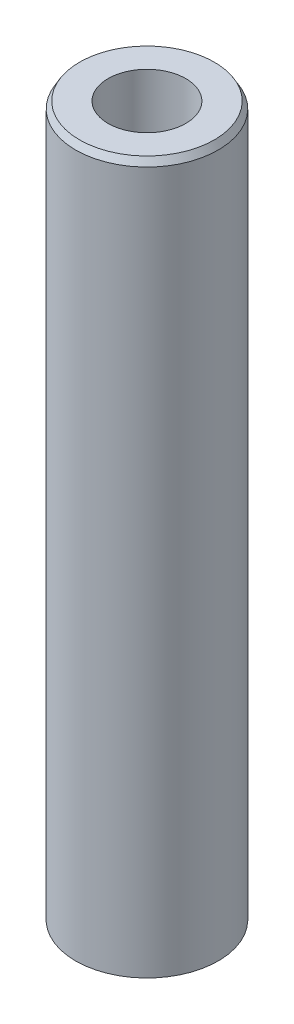
SolidWorks part; units mm, degrees
ref_plane "Front Plane" through (0, 0, 0) normal (0, 0, 1) x (1, 0, 0)
ref_plane "Top Plane" through (0, 0, 0) normal (0, 1, 0) x (1, 0, 0)
ref_plane "Right Plane" through (0, 0, 0) normal (1, 0, 0) x (0, 0, -1)
sketch "Sketch1" plane through (0, 0, 0) normal (0, 1, 0) x (1, 0, 0)
  circle A0 centre (0, 0) radius 60
  dimension "SHAFT_OD" = 120
extrude "Boss-Extrude1" add sketch "Sketch1" along normal blind 600
sketch "Sketch2" plane through (0, 0, 0) normal (0, 1, 0) x (1, 0, 0)
  circle A0 centre (0, 0) radius 32.7217
  dimension "BORE_D" = 65.4433
extrude "Cut-Extrude1" cut sketch "Sketch2" along normal through all
chamfer "Chamfer1" distance 5.7277 angle 30 2 edges at (0, 600, 60) (0, 0, 60) first distance on face at (0, 600, 60) first distance on face at (0, 0, 32.7217)
